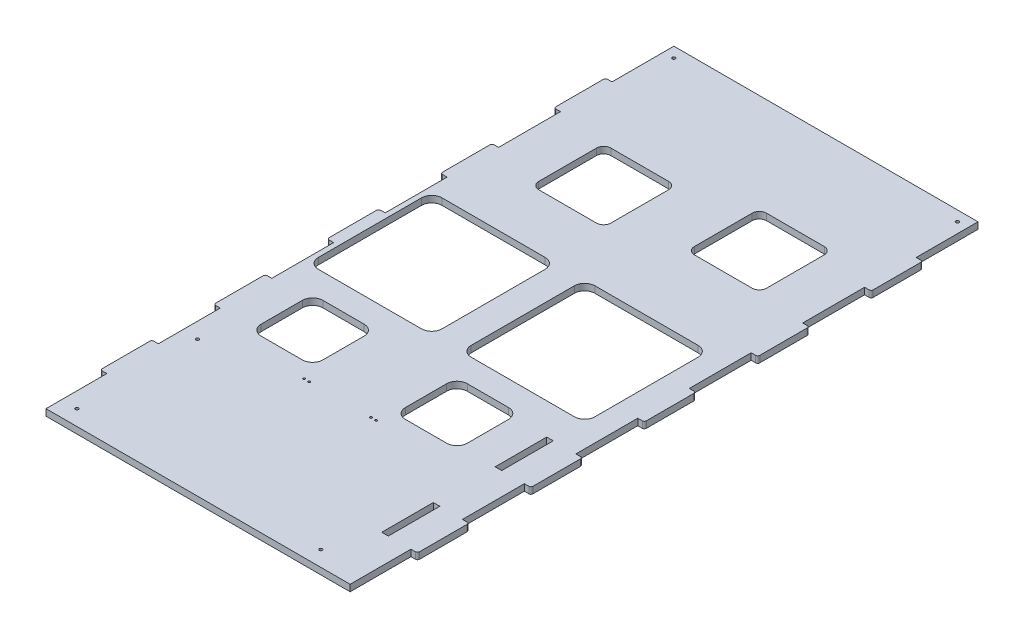
SolidWorks part; units mm, degrees
material "Beech"
ref_plane "Front Plane" through (0, 0, 0) normal (0, 0, 1) x (1, 0, 0)
ref_plane "Top Plane" through (0, 0, 0) normal (0, 1, 0) x (1, 0, 0)
ref_plane "Right Plane" through (0, 0, 0) normal (1, 0, 0) x (0, 0, -1)
sketch "Sketch1" plane through (0, 0, 0) normal (0, 1, 0) x (1, 0, 0)
  line L1 (0, 0) -> (295, 0)
  line L2 (0, 0) -> (0, 59)
  line L3 (0, 609) -> (295, 609)
  line L4 (295, 0) -> (295, 59)
  line L5 (0, 59) -> (-6.35, 59)
  line L7 (0, 109) -> (-6.35, 109)
  line L8 (-6.35, 59) -> (-6.35, 109)
  line L9 (0, 169) -> (-6.35, 169)
  line L10 (-6.35, 169) -> (-6.35, 219)
  line L11 (0, 219) -> (-6.35, 219)
  line L13 (0, 279) -> (-6.35, 279)
  line L14 (-6.35, 279) -> (-6.35, 329)
  line L15 (0, 329) -> (-6.35, 329)
  line L17 (0, 389) -> (-6.35, 389)
  line L18 (-6.35, 389) -> (-6.35, 439)
  line L19 (0, 439) -> (-6.35, 439)
  line L21 (0, 499) -> (-6.35, 499)
  line L22 (-6.35, 499) -> (-6.35, 549)
  line L23 (0, 549) -> (-6.35, 549)
  line L25 (295, 59) -> (301.35, 59)
  line L27 (295, 109) -> (301.35, 109)
  line L28 (301.35, 59) -> (301.35, 109)
  line L29 (295, 169) -> (301.35, 169)
  line L30 (301.35, 169) -> (301.35, 219)
  line L31 (295, 219) -> (301.35, 219)
  line L33 (295, 279) -> (301.35, 279)
  line L34 (301.35, 279) -> (301.35, 329)
  line L35 (295, 329) -> (301.35, 329)
  line L37 (295, 389) -> (301.35, 389)
  line L38 (301.35, 389) -> (301.35, 439)
  line L39 (295, 439) -> (301.35, 439)
  line L41 (295, 499) -> (301.35, 499)
  line L42 (301.35, 499) -> (301.35, 549)
  line L43 (295, 549) -> (301.35, 549)
  line L44 (0, 549) -> (0, 609)
  line L46 (0, 329) -> (0, 389)
  line L49 (0, 219) -> (0, 279)
  line L50 (0, 109) -> (0, 169)
  line L51 (295, 109) -> (295, 169)
  line L52 (295, 219) -> (295, 279)
  line L53 (295, 329) -> (295, 389)
  line L54 (295, 439) -> (295, 499)
  line L55 (295, 549) -> (295, 609)
  line L56 (0, 439) -> (0, 499)
  dimension "D1" = 609
  dimension "D2" = 295
  dimension "D3" = 6.35
  dimension "D4" = 50
  dimension "D5" = 59
  dimension "D7" = 60
  dimension "D8" = 50
  dimension "D9" = 6.35
  dimension "D11" = 59
  dimension "D12" = 60
  dimension "D6" = 5
  dimension "D10" = 5
extrude "Boss-Extrude1" add sketch "Sketch1" along normal blind 6.35
fillet "Fillet1" radius 2 20 edges at (301.35, 3.175, -549) (301.35, 3.175, -499) (301.35, 3.175, -439) (301.35, 3.175, -389) (301.35, 3.175, -329) (301.35, 3.175, -279) (301.35, 3.175, -219) (301.35, 3.175, -169) (301.35, 3.175, -109) (301.35, 3.175, -59) (-6.35, 3.175, -59) (-6.35, 3.175, -109) (-6.35, 3.175, -169) (-6.35, 3.175, -219) (-6.35, 3.175, -279) (-6.35, 3.175, -329) (-6.35, 3.175, -389) (-6.35, 3.175, -439) (-6.35, 3.175, -499) (-6.35, 3.175, -549)
sketch "Sketch2" plane through (0, 6.35, 0) normal (0, 1, 0) x (1, 0, 0)
  line L0 (266.65, 0) -> (266.65, 100) construction
  line L1 (0, 0) -> (295, 0) construction
  line L2 (0, 609) -> (0, 0) construction
  line L3 (295, 609) -> (295, 0) construction
  line L4 (0, 150) -> (266.65, 100) construction
  line L5 (266.65, 169) -> (266.65, 219)
  line L6 (266.65, 59) -> (273, 59)
  line L7 (266.65, 59) -> (266.65, 109)
  line L8 (266.65, 109) -> (273, 109)
  line L9 (273, 59) -> (273, 109)
  line L10 (266.65, 169) -> (273, 169)
  line L11 (273, 169) -> (273, 219)
  line L12 (266.65, 219) -> (273, 219)
  line L13 (0, 84.2124) -> (266.65, 84) construction
  line L14 (55.0424, 492.8768) -> (111.0424, 492.8768)
  line L15 (48.0424, 485.8768) -> (48.0424, 429.8768)
  line L16 (55.0424, 422.8768) -> (111.0424, 422.8768)
  line L17 (118.0424, 485.8768) -> (118.0424, 429.8768)
  line L18 (185.2335, 513.6581) -> (241.2335, 513.6581)
  line L19 (178.2335, 506.6581) -> (178.2335, 450.6581)
  line L20 (185.2335, 443.6581) -> (241.2335, 443.6581)
  line L21 (248.2335, 506.6581) -> (248.2335, 450.6581)
  line L22 (43.325, 225.298) -> (83.325, 225.298)
  line L23 (33.325, 215.298) -> (33.325, 175.298)
  line L24 (43.325, 165.298) -> (83.325, 165.298)
  line L25 (93.325, 215.298) -> (93.325, 175.298)
  line L26 (33.325, 225.298) -> (93.325, 165.298) construction
  line L27 (33.325, 165.298) -> (93.325, 225.298) construction
  line L32 (133.325, 0) -> (133.325, 609) construction
  line L33 (295, 609) -> (0, 609) construction
  line L34 (5, 369.1536) -> (125, 369.1536)
  line L35 (5, 369.1536) -> (5, 249.1536)
  line L36 (5, 249.1536) -> (125, 249.1536)
  line L37 (125, 369.1536) -> (125, 249.1536)
  line L38 (153, 369.4528) -> (273, 369.4528)
  line L39 (153, 369.4528) -> (153, 249.4528)
  line L40 (153, 249.4528) -> (273, 249.4528)
  line L41 (273, 369.4528) -> (273, 249.4528)
  line L42 (233.325, 165.298) -> (173.325, 225.298) construction
  line L43 (233.325, 225.298) -> (173.325, 165.298) construction
  line L44 (173.325, 215.298) -> (173.325, 175.298)
  line L45 (223.325, 165.298) -> (183.325, 165.298)
  line L46 (233.325, 215.298) -> (233.325, 175.298)
  line L47 (223.325, 225.298) -> (183.325, 225.298)
  line L48 (100, 150.298) -> (105, 150.298) construction
  line L49 (105, 150.298) -> (165, 150.298) construction
  line L50 (165, 150.298) -> (170, 150.298) construction
  arc A0 (48.0424, 429.8768) -> (55.0424, 422.8768) centre (55.0424, 429.8768) ccw
  arc A1 (111.0424, 422.8768) -> (118.0424, 429.8768) centre (111.0424, 429.8768) ccw
  arc A2 (111.0424, 492.8768) -> (118.0424, 485.8768) centre (111.0424, 485.8768) cw
  arc A3 (55.0424, 492.8768) -> (48.0424, 485.8768) centre (55.0424, 485.8768) ccw
  arc A4 (178.2335, 450.6581) -> (185.2335, 443.6581) centre (185.2335, 450.6581) ccw
  arc A5 (241.2335, 443.6581) -> (248.2335, 450.6581) centre (241.2335, 450.6581) ccw
  arc A6 (241.2335, 513.6581) -> (248.2335, 506.6581) centre (241.2335, 506.6581) cw
  arc A7 (185.2335, 513.6581) -> (178.2335, 506.6581) centre (185.2335, 506.6581) ccw
  arc A8 (33.325, 175.298) -> (43.325, 165.298) centre (43.325, 175.298) ccw
  arc A9 (83.325, 165.298) -> (93.325, 175.298) centre (83.325, 175.298) ccw
  arc A10 (83.325, 225.298) -> (93.325, 215.298) centre (83.325, 215.298) cw
  arc A11 (43.325, 225.298) -> (33.325, 215.298) centre (43.325, 215.298) ccw
  arc A16 (223.325, 225.298) -> (233.325, 215.298) centre (223.325, 215.298) cw
  arc A17 (183.325, 225.298) -> (173.325, 215.298) centre (183.325, 215.298) ccw
  arc A18 (183.325, 165.298) -> (173.325, 175.298) centre (183.325, 175.298) cw
  arc A19 (233.325, 175.298) -> (223.325, 165.298) centre (223.325, 175.298) cw
  circle A20 centre (15, 15) radius 1.5
  circle A21 centre (251.65, 15) radius 1.5
  circle A22 centre (15, 131.9259) radius 1.5
  circle A23 centre (10, 599) radius 1.5
  circle A24 centre (285, 599) radius 1.5
  circle A25 centre (100, 150.298) radius 1.025
  circle A26 centre (105, 150.298) radius 1.025
  circle A27 centre (165, 150.298) radius 1.025
  circle A28 centre (170, 150.298) radius 1.025
  point P33 (118.0424, 422.8768)
  point P36 (118.0424, 492.8768)
  point P39 (48.0424, 492.8768)
  point P42 (178.2335, 443.6581)
  point P47 (248.2335, 513.6581)
  point P50 (178.2335, 513.6581)
  point P51 (63.325, 195.298)
  point P74 (133.325, 84.1062)
  point P99 (203.325, 195.298)
  dimension "D10" = 7
  dimension "D11" = 7
  dimension "D16" = 10
  dimension "D17" = 70
  dimension "D22" = 3
  dimension "D25" = 3
  dimension "D28" = 3
  dimension "D18" = 3
  dimension "D31" = 3
  dimension "D40" = 2.05
  dimension "D42" = 2.05
  dimension "D43" = 2.05
  dimension "D44" = 2.05
  dimension "D1" = 100
  dimension "D2" = 150
  dimension "D3" = 6.35
  dimension "D4" = 50
  dimension "D6" = 70
  dimension "D7" = 70
  dimension "D8" = 70
  dimension "D9" = 70
  dimension "D12" = 60
  dimension "D13" = 60
  dimension "D14" = 22
  dimension "D15" = 59
  dimension "12" = 120
  dimension "D19" = 120
  dimension "D20" = 120
  dimension "D21" = 120
  dimension "D23" = 15
  dimension "D24" = 15
  dimension "D26" = 15
  dimension "D27" = 15
  dimension "D29" = 15
  dimension "D30" = 15
  dimension "D32" = 10
  dimension "D33" = 10
  dimension "D34" = 10
  dimension "D35" = 10
  dimension "D36" = 5
  dimension "D37" = 22
  dimension "D38" = 15
  dimension "D39" = 200
  dimension "D41" = 5
  dimension "D45" = 5
  dimension "D46" = 60
  dimension "D5" = 2
extrude "Cut-Extrude1" cut sketch "Sketch2" against normal blind 6.35
fillet "Fillet2" radius 10 8 edges at (125, 3.175, -249.1536) (5, 3.175, -249.1536) (5, 3.175, -369.1536) (125, 3.175, -369.1536) (153, 3.175, -249.4528) (273, 3.175, -249.4528) (273, 3.175, -369.4528) (153, 3.175, -369.4528)
